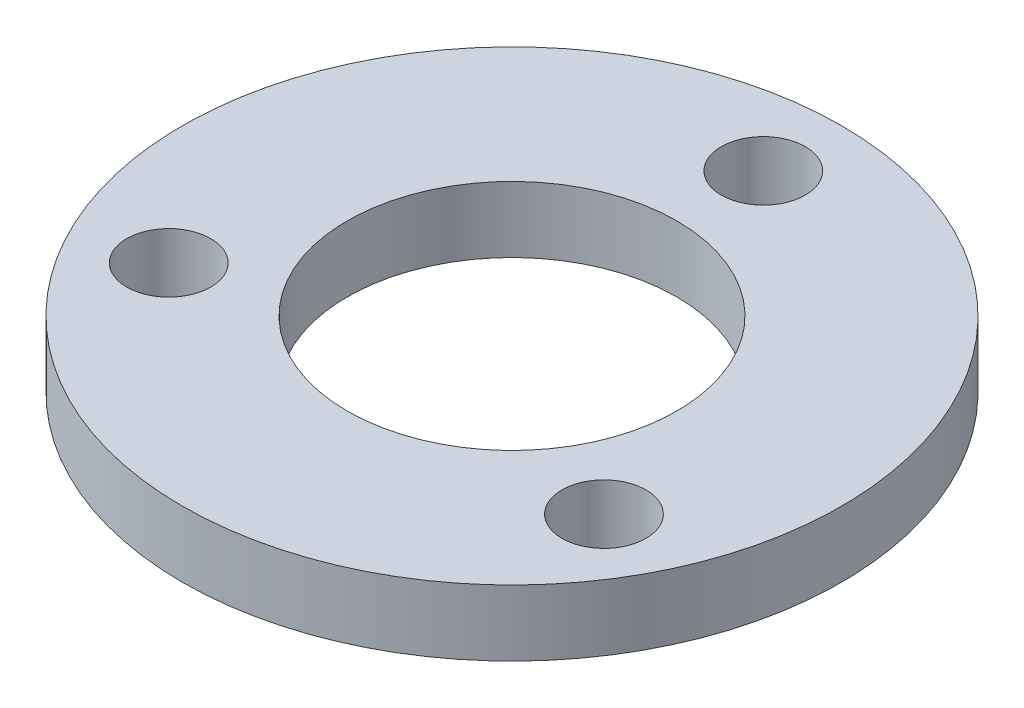
SolidWorks part; units mm, degrees
ref_plane "Front Plane" through (0, 0, 0) normal (0, 0, 1) x (1, 0, 0)
ref_plane "Top Plane" through (0, 0, 0) normal (0, 1, 0) x (1, 0, 0)
ref_plane "Right Plane" through (0, 0, 0) normal (1, 0, 0) x (0, 0, -1)
sketch "Sketch1" plane through (0, 0, 0) normal (0, 1, 0) x (1, 0, 0)
  circle A0 centre (0, 0) radius 20
  circle A2 centre (0, 0) radius 10
  dimension "D1" = 40
  dimension "D2" = 20
extrude "Boss-Extrude1" add sketch "Sketch1" along normal blind 4
sketch "Sketch2" plane through (0, 4, 0) normal (0, 1, 0) x (1, 0, 0)
  circle A0 centre (0, 0) radius 15.25 construction
  circle A1 centre (0, 15.25) radius 2.55
  dimension "D1" = 5.1
  dimension "D2" = 30.5
extrude "Cut-Extrude2" cut sketch "Sketch2" against normal through all
pattern_circular "CirPattern1" count 3 over 360 about axis through (0, 4, 0) along (0, -1, 0) of "Cut-Extrude2" reverse direction yes
